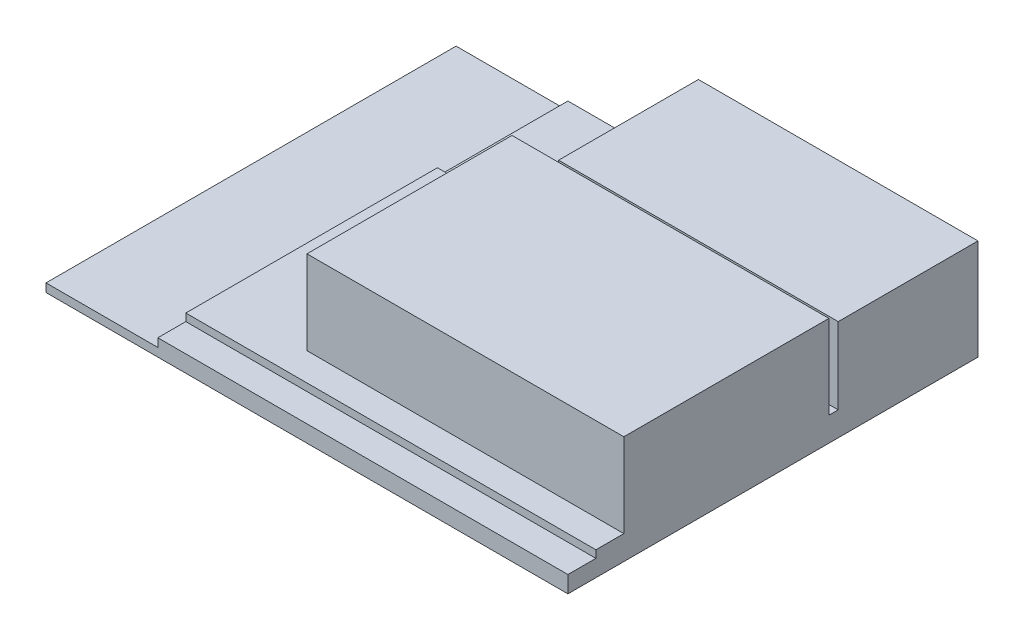
SolidWorks part; units mm, degrees
ref_plane "Front Plane" through (0, 0, 0) normal (0, 0, 1) x (1, 0, 0)
ref_plane "Top Plane" through (0, 0, 0) normal (0, 1, 0) x (1, 0, 0)
ref_plane "Right Plane" through (0, 0, 0) normal (1, 0, 0) x (0, 0, -1)
sketch "Sketch1" plane through (0, 0, 0) normal (0, 1, 0) x (1, 0, 0)
  line L1 (-128.3019, 71.5094) -> (91.6981, 71.5094)
  line L2 (-128.3019, 71.5094) -> (-128.3019, -148.4906)
  line L3 (-128.3019, -148.4906) -> (91.6981, -148.4906)
  line L4 (91.6981, 71.5094) -> (91.6981, -148.4906)
  dimension "D1" = 220
  dimension "D2" = 220
extrude "Boss-Extrude1" add sketch "Sketch1" along normal blind 4.5
sketch "Sketch2" plane through (0, 4.5, 0) normal (0, 1, 0) x (1, 0, 0)
  line L0 (-128.3019, -133.4906) -> (91.6981, -133.4906)
  line L1 (-128.3019, 71.5094) -> (-128.3019, -148.4906) construction
  line L2 (91.6981, -148.4906) -> (91.6981, 71.5094) construction
  line L3 (91.6981, -133.4906) -> (91.6981, 1.5094)
  line L4 (91.6981, 1.5094) -> (-128.3019, 1.5094)
  line L5 (-128.3019, 1.5094) -> (-128.3019, -133.4906)
  line L6 (-128.3019, -148.4906) -> (91.6981, -148.4906) construction
  dimension "D1" = 15
  dimension "D2" = 150
extrude "Boss-Extrude2" add sketch "Sketch2" along normal blind 4
sketch "Sketch3" plane through (0, 4.5, 0) normal (0, 1, 0) x (1, 0, 0)
  line L0 (91.6981, 1.5094) -> (91.6981, 71.5094) construction
  line L1 (-58.3019, 71.5094) -> (91.6981, 71.5094)
  line L2 (-58.3019, 71.5094) -> (-58.3019, -3.4906)
  line L3 (-58.3019, -3.4906) -> (91.6981, -3.4906)
  line L4 (91.6981, 71.5094) -> (91.6981, -3.4906)
  line L5 (91.6981, 71.5094) -> (-128.3019, 71.5094) construction
  dimension "D1" = 150
  dimension "D2" = 75
extrude "Boss-Extrude3" add sketch "Sketch3" along normal blind 45
sketch "Sketch4" plane through (0, 8.5, 0) normal (0, 1, 0) x (1, 0, 0)
  line L0 (91.6981, -133.4906) -> (91.6981, -3.4906) construction
  line L1 (-78.3019, -8.4906) -> (91.6981, -8.4906)
  line L2 (-78.3019, -8.4906) -> (-78.3019, -118.4906)
  line L3 (-78.3019, -118.4906) -> (91.6981, -118.4906)
  line L4 (91.6981, -8.4906) -> (91.6981, -118.4906)
  line L5 (-128.3019, -148.4906) -> (91.6981, -148.4906) construction
  dimension "D1" = 170
  dimension "D2" = 140
  dimension "D3" = 110
extrude "Boss-Extrude4" add sketch "Sketch4" along normal blind 45
sketch "Sketch5" plane through (0, 0, 0) normal (0, -1, 0) x (1, 0, 0)
  line L0 (91.6981, -71.5094) -> (-128.3019, -71.5094) construction
  line L1 (91.6981, 148.4906) -> (-188.3019, 148.4906)
  line L2 (91.6981, 148.4906) -> (91.6981, -71.5094)
  line L3 (91.6981, -71.5094) -> (-188.3019, -71.5094)
  line L4 (-188.3019, 148.4906) -> (-188.3019, -71.5094)
  line L5 (-128.3019, -71.5094) -> (-128.3019, 148.4906) construction
  dimension "D1" = 60
extrude "Boss-Extrude5" add sketch "Sketch5" along normal blind 4.5 contours L4 L3 L2 L1
